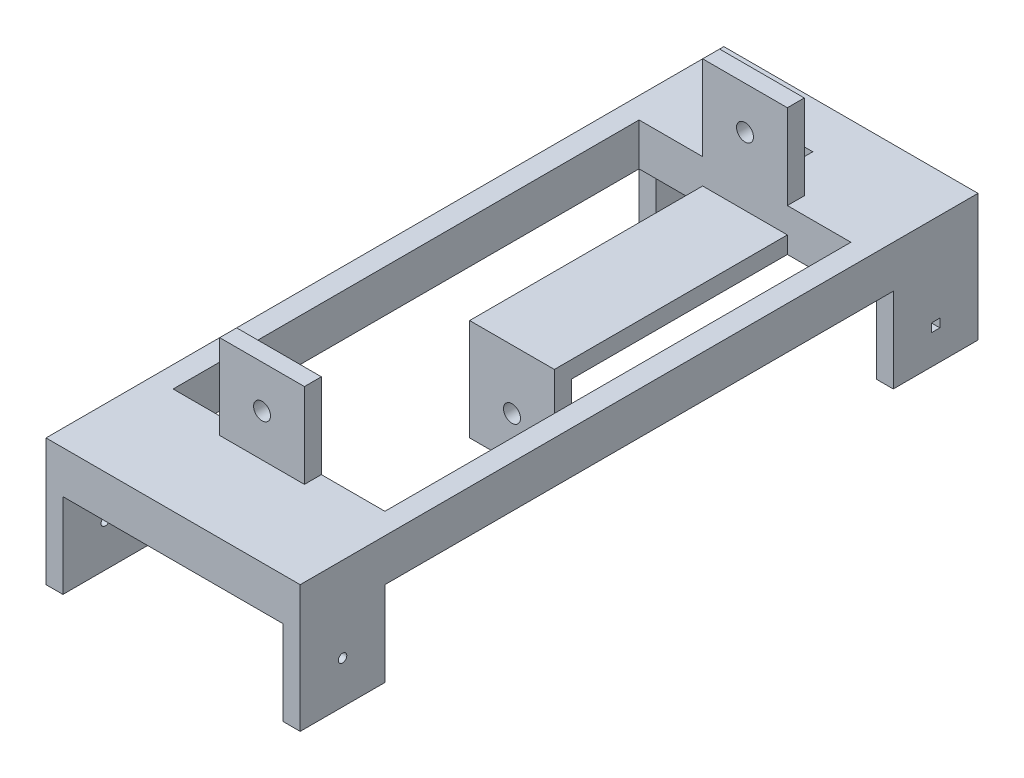
SolidWorks part; units mm, degrees
other "Markup1"
sketch "Sketch19" plane through (-15, 15, -40) normal (-0.0389, 0.0826, -0.9958) x (-0.519, -0.8533, -0.0505)
ref_plane "Front Plane" through (0, 0, 0) normal (0, 0, 1) x (1, 0, 0)
ref_plane "Top Plane" through (0, 0, 0) normal (0, 1, 0) x (1, 0, 0)
ref_plane "Right Plane" through (0, 0, 0) normal (1, 0, 0) x (0, 0, -1)
sketch "Sketch1" plane through (0, 0, 0) normal (0, 1, 0) x (1, 0, 0)
  line L1 (-15, 40) -> (15, 40)
  line L2 (-15, 40) -> (-15, -40)
  line L3 (-15, -40) -> (15, -40)
  line L4 (15, 40) -> (15, -40)
  line L5 (-15, 40) -> (15, -40) construction
  line L6 (-15, -40) -> (15, 40) construction
  point P0 (0, 0)
  dimension "D1" = 30
  dimension "D2" = 80
extrude "Boss-Extrude1" add sketch "Sketch1" along normal blind 5
sketch "Sketch2" plane through (15, 0, 0) normal (1, 0, 0) x (0, 0, -1)
  line L1 (-40, 0) -> (-30, 0)
  line L2 (-40, 0) -> (-40, -10)
  line L3 (-40, -10) -> (-30, -10)
  line L4 (-30, 0) -> (-30, -10)
  line L5 (40, 0) -> (30, 0)
  line L6 (40, 0) -> (40, -10)
  line L7 (40, -10) -> (30, -10)
  line L8 (30, 0) -> (30, -10)
  dimension "D1" = 10
  dimension "D2" = 10
  dimension "D3" = 10
  dimension "D4" = 10
extrude "Boss-Extrude2" add sketch "Sketch2" against normal blind 30
sketch "Sketch3" plane through (15, 0, 0) normal (1, 0, 0) x (0, 0, -1)
  line L0 (-40, 5) -> (-40, -10) construction
  line L2 (-40, -10) -> (-30, -10) construction
  line L5 (34.5, -6.5) -> (35.5, -6.5)
  line L6 (34.5, -6.5) -> (34.5, -5.5)
  line L7 (34.5, -5.5) -> (35.5, -5.5)
  line L8 (35.5, -6.5) -> (35.5, -5.5)
  line L9 (34.5, -6.5) -> (35.5, -5.5) construction
  line L10 (34.5, -5.5) -> (35.5, -6.5) construction
  line L12 (30, 0) -> (30, -10) construction
  line L14 (30, -10) -> (40, -10) construction
  circle A0 centre (-35, -5) radius 0.5
  point P3 (35, -6)
  point P12 (35.0655, -10)
  dimension "D1" = 1
  dimension "D2" = 5
  dimension "D3" = 5
  dimension "D4" = 5
  dimension "D5" = 3.5
  dimension "D7" = 1
extrude "Cut-Extrude1" cut sketch "Sketch3" against normal through all both and the other way through all
sketch "Sketch4" plane through (0, 5, 0) normal (0, 1, 0) x (1, 0, 0)
  line L9 (-12.5, -27.5) -> (12.5, -27.5)
  line L10 (-12.5, -27.5) -> (-12.5, 27.5)
  line L11 (-12.5, 27.5) -> (12.5, 27.5)
  line L12 (12.5, -27.5) -> (12.5, 27.5)
  line L13 (-12.5, -27.5) -> (12.5, 27.5) construction
  line L14 (-12.5, 27.5) -> (12.5, -27.5) construction
  point P0 (0, 0)
  dimension "D1" = 55
  dimension "D2" = 25
extrude "Cut-Extrude2" cut sketch "Sketch4" against normal through all both and the other way through all
sketch "Sketch5" plane through (0, 0, -40) normal (0, 0, -1) x (-1, 0, 0)
  line L0 (15, -10) -> (-15, -10) construction
  line L1 (-13, -10) -> (13, -10)
  line L2 (-13, -10) -> (-13, 0)
  line L3 (-13, 0) -> (13, 0)
  line L4 (13, -10) -> (13, 0)
  line L5 (-15, 5) -> (-15, -10) construction
  line L6 (15, 5) -> (15, -10) construction
  dimension "D1" = 10
  dimension "D2" = 2
  dimension "D3" = 2
extrude "Cut-Extrude3" cut sketch "Sketch5" against normal through all both and the other way through all
sketch "Sketch6" plane through (0, 0, -40) normal (0, 0, -1) x (-1, 0, 0)
  line L0 (-13, 0) -> (13, 0) construction
  line L1 (-5, 0) -> (5, 0)
  line L2 (-5, 0) -> (-5, -10)
  line L3 (-5, -10) -> (5, -10)
  line L4 (5, 0) -> (5, -10)
  line L6 (-13, -10) -> (-13, 0) construction
  line L7 (13, 0) -> (13, -10) construction
  dimension "D1" = 8
  dimension "D2" = 10
  dimension "D3" = 8
extrude "Boss-Extrude3" add sketch "Sketch6" against normal blind 80
sketch "Sketch7" plane through (0, 0, -40) normal (0, 0, -1) x (-1, 0, 0)
  line L0 (-5, 0) -> (-5, -10) construction
  line L1 (-5, -10) -> (5, -10) construction
  circle A0 centre (0, -5) radius 1
  point P4 (-5, -5)
  dimension "D1" = 2
  dimension "D2" = 5
  dimension "D3" = 5
extrude "Cut-Extrude4" cut sketch "Sketch7" against normal through all both and the other way through all
sketch "Sketch8" plane through (5, 0, 0) normal (1, 0, 0) x (0, 0, -1)
  line L0 (-40, -10) -> (40, -10) construction
  line L1 (-28, -10) -> (28, -10)
  line L2 (-28, -10) -> (-28, 0)
  line L3 (-28, 0) -> (28, 0)
  line L4 (28, -10) -> (28, 0)
  line L5 (-27.5, 0) -> (27.5, 0) construction
  line L6 (-30, -10) -> (-30, 0) construction
  line L7 (30, 0) -> (30, -10) construction
  dimension "D1" = 2
  dimension "D2" = 2
extrude "Cut-Extrude5" cut sketch "Sketch8" against normal through all both and the other way through all
sketch "Sketch9" plane through (0, 0, 40) normal (0, 0, 1) x (1, 0, 0)
  line L1 (-5, -10) -> (5, -10)
  line L2 (-5, -10) -> (-5, 0)
  line L3 (-5, 0) -> (5, 0)
  line L4 (5, -10) -> (5, 0)
extrude "Cut-Extrude6" cut sketch "Sketch9" against normal blind 10
sketch "Sketch10" plane through (0, 0, -40) normal (0, 0, -1) x (-1, 0, 0)
  line L1 (-5, -10) -> (5, -10)
  line L2 (-5, -10) -> (-5, 0)
  line L3 (-5, 0) -> (5, 0)
  line L4 (5, -10) -> (5, 0)
extrude "Cut-Extrude7" cut sketch "Sketch10" against normal blind 10
sketch "Sketch12" plane through (0, 5, 0) normal (0, 1, 0) x (1, 0, 0)
  line L0 (-12.5, -27.5) -> (12.5, -27.5) construction
  line L1 (-5, -27.5) -> (5, -27.5)
  line L2 (-5, -27.5) -> (-5, -29.5)
  line L3 (-5, -29.5) -> (5, -29.5)
  line L4 (5, -27.5) -> (5, -29.5)
  line L5 (12.5, 27.5) -> (-12.5, 27.5) construction
  line L6 (5, 27.5) -> (-5, 27.5)
  line L7 (5, 27.5) -> (5, 29.5)
  line L8 (5, 29.5) -> (-5, 29.5)
  line L9 (-5, 27.5) -> (-5, 29.5)
  line L10 (15, -40) -> (15, 40) construction
  dimension "D1" = 2
  dimension "D2" = 10
  dimension "D3" = 10
  dimension "D4" = 2
  dimension "D5" = 10
  dimension "D6" = 10
extrude "Boss-Extrude5" add sketch "Sketch12" along normal blind 10
sketch "Sketch13" plane through (0, 0, 29.5) normal (0, 0, 1) x (1, 0, 0)
  line L0 (-5, 15) -> (-5, 5) construction
  line L1 (-5, 5) -> (5, 5) construction
  circle A0 centre (0, 10) radius 1
  dimension "D1" = 2
  dimension "D2" = 5
  dimension "D3" = 5
extrude "Cut-Extrude8" cut sketch "Sketch13" against normal through all both and the other way through all contours A0
sketch "Sketch15" plane through (0, 5, 0) normal (0, 1, 0) x (1, 0, 0)
  line L0 (5, 29.5) -> (-5, 29.5) construction
  line L1 (-1, 32.5) -> (1, 32.5)
  line L2 (-1, 32.5) -> (-1, 34.5)
  line L3 (-1, 34.5) -> (1, 34.5)
  line L4 (1, 32.5) -> (1, 34.5)
  line L5 (-1, 32.5) -> (1, 34.5) construction
  line L6 (-1, 34.5) -> (1, 32.5) construction
  line L7 (5, 27.5) -> (5, 29.5) construction
  point P0 (0, 33.5)
  dimension "D1" = 2
  dimension "D2" = 2
  dimension "D3" = 4
  dimension "D4" = 4
extrude "Cut-Extrude11" cut sketch "Sketch15" against normal through all both and the other way through all
sketch "Sketch16" plane through (0, 0, -30) normal (0, 0, -1) x (-1, 0, 0)
  line L4 (-5, 0) -> (-5, -10)
  line L5 (-5, -10) -> (5, -10)
  line L6 (5, -10) -> (5, 0)
  line L7 (5, 0) -> (-5, 0)
  line L8 (-5, 0) -> (-5, -10)
  line L9 (-5, -10) -> (5, -10)
  line L10 (5, -10) -> (5, 0)
  line L11 (5, 0) -> (-5, 0)
  dimension "D1" = 0
extrude "Boss-Extrude6" add sketch "Sketch16" against normal blind 30
sketch "Sketch17" plane through (0, 0, -30) normal (0, 0, -1) x (-1, 0, 0)
  line L1 (-5, -10) -> (5, -10)
  line L2 (-5, -10) -> (-5, 0)
  line L3 (-5, 0) -> (5, 0)
  line L4 (5, -10) -> (5, 0)
extrude "Cut-Extrude12" cut sketch "Sketch17" against normal blind 28
sketch "Sketch18" plane through (0, 0, -2) normal (0, 0, -1) x (-1, 0, 0)
  line L0 (-5, -10) -> (5, -10) construction
  line L2 (-5, 0) -> (-5, -10) construction
  circle A0 centre (0, -5) radius 1
  dimension "D3" = 2
  dimension "D1" = 5
  dimension "D2" = 5
extrude "Cut-Extrude13" cut sketch "Sketch18" against normal through all both and the other way through all
sketch "Sketch20" plane through (0, 0, -40) normal (0, 0, -1) x (-1, 0, 0)
  line L1 (-5, 0) -> (5, 0)
  line L2 (-5, 0) -> (-5, 2)
  line L3 (-5, 2) -> (5, 2)
  line L4 (5, 0) -> (5, 2)
  dimension "D1" = 10
  dimension "D2" = 2
extrude "Boss-Extrude7" add sketch "Sketch20" against normal blind 40
equation "\"w\"=3.9113"
